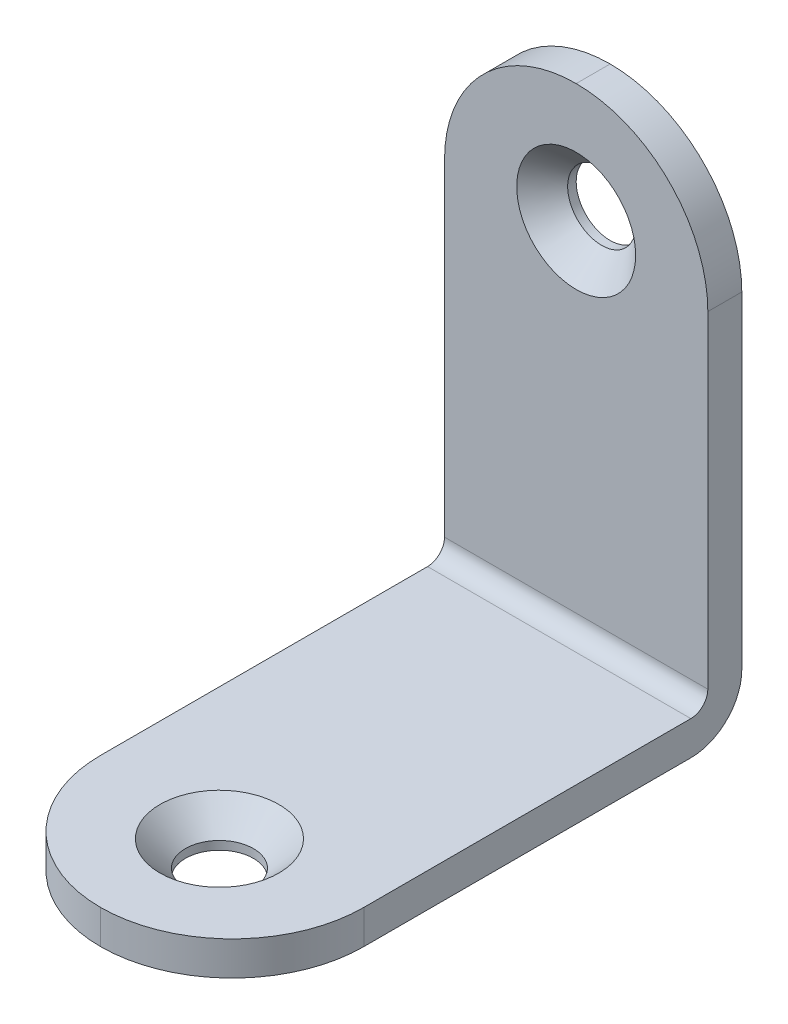
SolidWorks part; units mm, degrees
ref_plane "前视基准面" through (0, 0, 0) normal (0, 0, 1) x (1, 0, 0)
ref_plane "上视基准面" through (0, 0, 0) normal (0, 1, 0) x (1, 0, 0)
ref_plane "右视基准面" through (0, 0, 0) normal (1, 0, 0) x (0, 0, -1)
sketch "草图1" plane through (0, 0, 0) normal (1, 0, 0) x (0, 0, -1)
  line L0 (-30, 0) -> (-3, 0)
  line L1 (0, 3) -> (0, 30)
  line L2 (-30, 2) -> (-3, 2)
  line L3 (-2, 3) -> (-2, 30)
  line L4 (-30, 0) -> (-30, 2)
  line L5 (0, 30) -> (-2, 30)
  arc A0 (-3, 0) -> (0, 3) centre (-3, 3) ccw
  arc A1 (-3, 2) -> (-2, 3) centre (-3, 3) ccw
  point P10 (0, 0)
  dimension "D1" = 30
  dimension "D2" = 30
  dimension "D3" = 2
extrude "凸台-拉伸1" add sketch "草图1" along normal blind 7.75 and the other way blind 7.75
sketch "草图3" plane through (0, 2, 0) normal (0, 1, 0) x (1, 0, 0)
  line L0 (0, 5.2738) -> (0, -33.0015) construction
  line L3 (-7.75, -30) -> (7.75, -30) construction
  circle A0 centre (0, -23) radius 2
  dimension "D1" = 4
  dimension "D2" = 7
extrude "切除-拉伸2" cut sketch "草图3" against normal blind 15.5
sketch "草图4" plane through (0, 0, 2) normal (0, 0, 1) x (1, 0, 0)
  line L0 (0, -4.5637) -> (0, 33.2855) construction
  line L2 (-7.75, 30) -> (7.75, 30) construction
  circle A0 centre (0, 23) radius 2
  dimension "D1" = 4
  dimension "D2" = 7
extrude "切除-拉伸3" cut sketch "草图4" against normal blind 15.5
fillet "圆角1" radius 7.75 4 edges at (7.75, 30, 1) (-7.75, 30, 1) (7.75, 1, 30) (-7.75, 1, 30)
chamfer "倒角1" distance 1.5 angle 45 2 edges at (2, 23, 2) (0, 2, 25)
